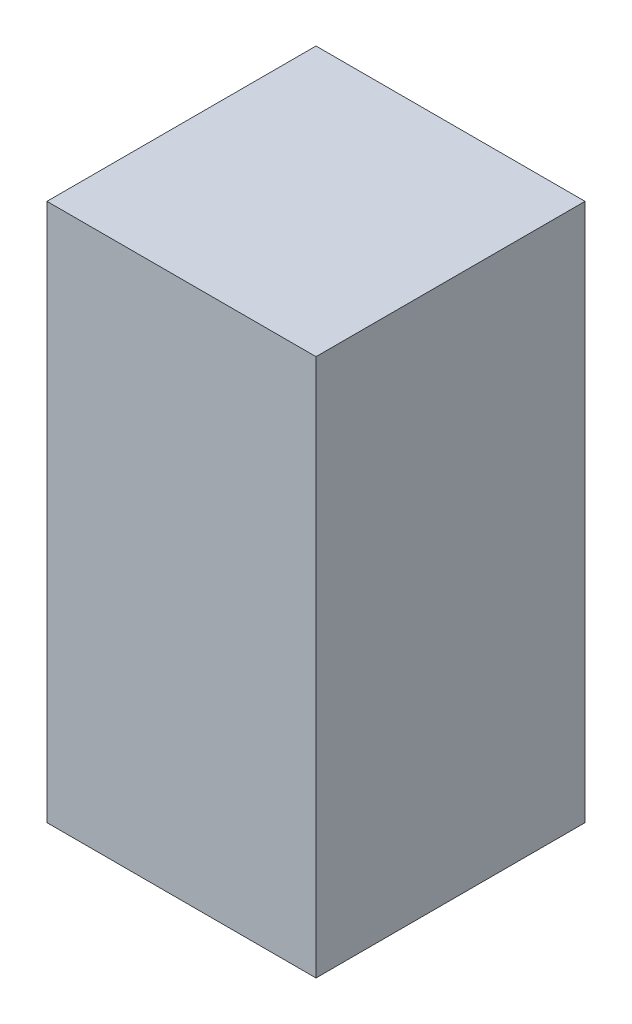
SolidWorks part; units mm, degrees
ref_plane "Front Plane" through (0, 0, 0) normal (0, 0, 1) x (1, 0, 0)
ref_plane "Top Plane" through (0, 0, 0) normal (0, 1, 0) x (1, 0, 0)
ref_plane "Right Plane" through (0, 0, 0) normal (1, 0, 0) x (0, 0, -1)
sketch "Sketch1" plane through (0, 0, 0) normal (0, 1, 0) x (1, 0, 0)
  line L1 (-3.25, 3.25) -> (3.25, 3.25)
  line L2 (-3.25, 3.25) -> (-3.25, -3.25)
  line L3 (-3.25, -3.25) -> (3.25, -3.25)
  line L4 (3.25, 3.25) -> (3.25, -3.25)
  line L5 (-3.25, 3.25) -> (3.25, -3.25) construction
  line L6 (-3.25, -3.25) -> (3.25, 3.25) construction
  point P0 (0, 0)
  dimension "D1" = 6.5
extrude "Boss-Extrude1" add sketch "Sketch1" along normal blind 13
